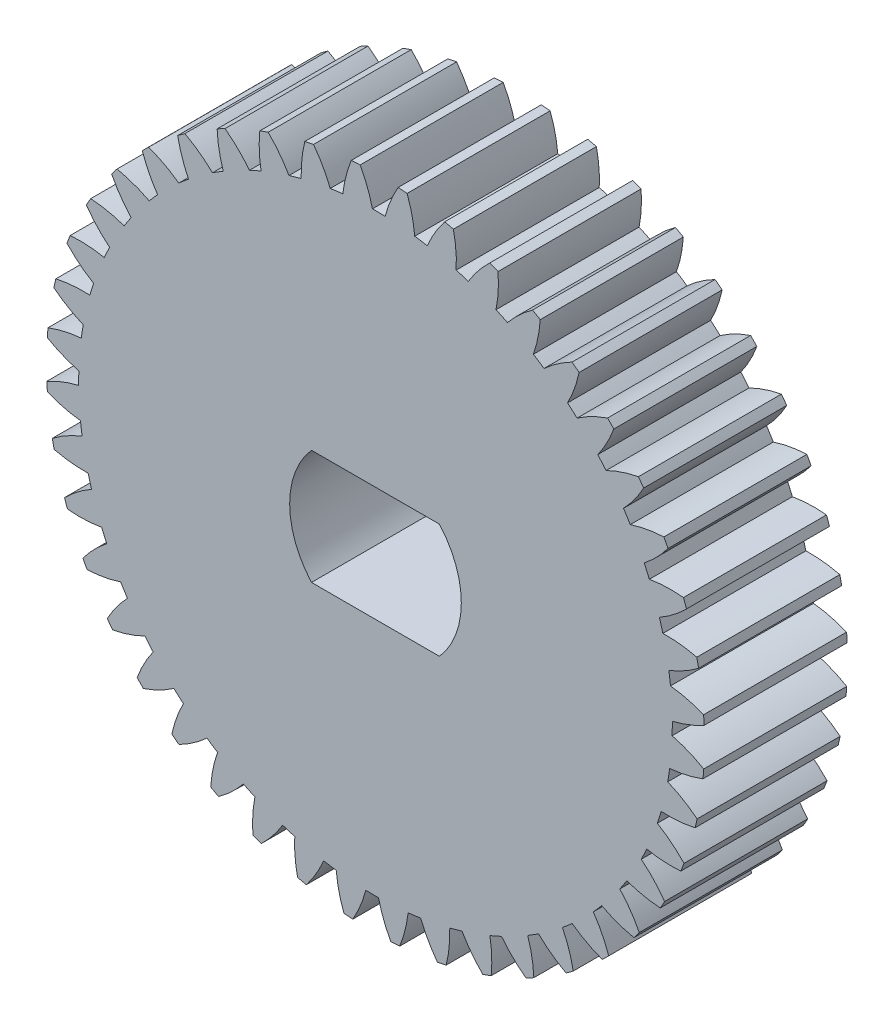
SolidWorks part; units mm, degrees
ref_plane "Front Plane" through (0, 0, 0) normal (0, 0, 1) x (1, 0, 0)
ref_plane "Top Plane" through (0, 0, 0) normal (0, 1, 0) x (1, 0, 0)
ref_plane "Right Plane" through (0, 0, 0) normal (1, 0, 0) x (0, 0, -1)
sketch "Sketch1" plane through (0, 0, 0) normal (0, 0, 1) x (1, 0, 0)
  circle A0 centre (0, 0) radius 57.1163
extrude "Boss-Extrude1" add sketch "Sketch1" along normal blind 10
extrude "Cut-Extrude5" cut sketch "Sketch6" against normal through all both and the other way through all contours A176 A703 A702 A701 A700 A699 A698 A697 A696 A695 A694 A693 A692 A691 A690 A689 A688 A687 A686 A685 A684 A683 A682 A681 A680 A679 A678 A677 A676 A675 A674 A673 A672 A671 A670 A669 A668 A667 A666 A665 A664 A663 A662 A661 A660 A659 A658 A657 A656 A655 | L0 A177 L1 A0 region at (13.1698, 8.2293, -42.7823) region at (-98.2995, 8.2293, -42.7823)
sketch "Sketch6" plane through (-165.342, -142.9681, -42.7823) normal (0, 0, 1) x (1, 0, 0)
  line L0 (174.0397, 155.1974) -> (182.984, 155.1974)
  line L1 (174.0397, 147.1974) -> (182.984, 147.1974)
  arc A0 (182.984, 147.1974) -> (182.984, 155.1974) centre (178.5118, 151.1974) ccw
  circle A176 centre (178.5118, 151.1974) radius 114.7139
  arc A177 (174.0397, 155.1974) -> (174.0397, 147.1974) centre (178.5118, 151.1974) ccw
  arc A528 (175.3501, 171.7041) -> (174.1813, 173.786) centre (167.1631, 168.4771) ccw
  arc A529 (174.1813, 173.786) -> (173.5696, 173.6601) centre (178.5118, 151.1974) ccw
  arc A530 (173.5696, 173.6601) -> (173.3181, 171.2858) centre (182.114, 171.5544) ccw
  arc A531 (173.3181, 171.2858) -> (172.4639, 171.0454) centre (178.5118, 151.1974) ccw
  arc A532 (172.4639, 171.0454) -> (171.0107, 172.9398) centre (164.8195, 166.6862) ccw
  arc A533 (171.0107, 172.9398) -> (170.4232, 172.7281) centre (178.5118, 151.1974) ccw
  arc A534 (170.4232, 172.7281) -> (170.5121, 170.3422) centre (179.1802, 171.8598) ccw
  arc A535 (170.5121, 170.3422) -> (169.7008, 169.9827) centre (178.5118, 151.1974) ccw
  arc A536 (169.7008, 169.9827) -> (167.9928, 171.651) centre (162.7545, 164.5799) ccw
  arc A537 (167.9928, 171.651) -> (167.4414, 171.3579) centre (178.5118, 151.1974) ccw
  arc A538 (167.4414, 171.3579) -> (167.8689, 169.0089) centre (176.2328, 171.7446) ccw
  arc A539 (167.8689, 169.0089) -> (167.117, 168.5375) centre (178.5118, 151.1974) ccw
  arc A540 (167.117, 168.5375) -> (165.189, 169.9458) centre (161.0104, 162.2012) ccw
  arc A541 (165.189, 169.9458) -> (164.6849, 169.5772) centre (178.5118, 151.1974) ccw
  arc A542 (164.6849, 169.5772) -> (165.4424, 167.3129) centre (173.3319, 171.2112) ccw
  arc A543 (165.4424, 167.3129) -> (164.7653, 166.7394) centre (178.5118, 151.1974) ccw
  arc A544 (164.7653, 166.7394) -> (162.6564, 167.8589) centre (159.6225, 159.5985) ccw
  arc A545 (162.6564, 167.8589) -> (162.2099, 167.4223) centre (178.5118, 151.1974) ccw
  arc A546 (162.2099, 167.4223) -> (163.2819, 165.2889) centre (170.5363, 170.2703) ccw
  arc A547 (163.2819, 165.2889) -> (162.6933, 164.6248) centre (178.5118, 151.1974) ccw
  arc A548 (162.6933, 164.6248) -> (160.4466, 165.4329) centre (158.6192, 156.8247) ccw
  arc A549 (160.4466, 165.4329) -> (160.0668, 164.9372) centre (178.5118, 151.1974) ccw
  arc A550 (160.0668, 164.9372) -> (161.4315, 162.9781) centre (167.9032, 168.9411) ccw
  arc A551 (161.4315, 162.9781) -> (160.9434, 162.2369) centre (178.5118, 151.1974) ccw
  arc A552 (160.9434, 162.2369) -> (158.6046, 162.717) centre (158.0208, 153.9364) ccw
  arc A553 (158.6046, 162.717) -> (158.2992, 162.1723) centre (178.5118, 151.1974) ccw
  arc A554 (158.2992, 162.1723) -> (159.9288, 160.4274) centre (165.486, 167.2507) ccw
  arc A555 (159.9288, 160.4274) -> (159.5511, 159.6243) centre (178.5118, 151.1974) ccw
  arc A556 (159.5511, 159.6243) -> (157.1678, 159.7667) centre (157.8396, 150.9924) ccw
  arc A557 (157.1678, 159.7667) -> (156.943, 159.184) centre (178.5118, 151.1974) ccw
  arc A558 (156.943, 159.184) -> (158.8044, 157.6888) centre (163.3339, 165.2335) ccw
  arc A559 (158.8044, 157.6888) -> (158.5448, 156.8402) centre (178.5118, 151.1974) ccw
  arc A560 (158.5448, 156.8402) -> (156.1655, 156.6419) centre (158.0792, 148.0525) ccw
  arc A561 (156.1655, 156.6419) -> (156.0259, 156.0332) centre (178.5118, 151.1974) ccw
  arc A562 (156.0259, 156.0332) -> (158.0812, 154.818) centre (161.4908, 162.9306) ccw
  arc A563 (158.0812, 154.818) -> (157.945, 153.9411) centre (178.5118, 151.1974) ccw
  arc A564 (157.945, 153.9411) -> (155.6181, 153.4063) centre (158.7347, 145.1766) ccw
  arc A565 (155.6181, 153.4063) -> (155.5666, 152.7839) centre (178.5118, 151.1974) ccw
  arc A566 (155.5666, 152.7839) -> (157.7738, 151.8736) centre (159.9943, 160.3889) ccw
  arc A567 (157.7738, 151.8736) -> (157.7639, 150.9863) centre (178.5118, 151.1974) ccw
  arc A568 (157.7639, 150.9863) -> (155.5368, 150.1257) centre (159.7929, 142.4234) ccw
  arc A569 (155.5368, 150.1257) -> (155.5744, 149.5023) centre (178.5118, 151.1974) ccw
  arc A570 (155.5744, 149.5023) -> (157.8887, 148.9154) centre (158.8747, 157.66) ccw
  arc A571 (157.8887, 148.9154) -> (158.0051, 148.0357) centre (178.5118, 151.1974) ccw
  arc A572 (158.0051, 148.0357) -> (155.9232, 146.8669) centre (161.2321, 139.8487) ccw
  arc A573 (155.9232, 146.8669) -> (156.0491, 146.2552) centre (178.5118, 151.1974) ccw
  arc A574 (156.0491, 146.2552) -> (158.4234, 146.0037) centre (158.1548, 154.7996) ccw
  arc A575 (158.4234, 146.0037) -> (158.6638, 145.1494) centre (178.5118, 151.1974) ccw
  arc A576 (158.6638, 145.1494) -> (156.7694, 143.6963) centre (163.0231, 137.505) ccw
  arc A577 (156.7694, 143.6963) -> (156.9811, 143.1087) centre (178.5118, 151.1974) ccw
  arc A578 (156.9811, 143.1087) -> (159.367, 143.1976) centre (157.8494, 151.8658) ccw
  arc A579 (159.367, 143.1976) -> (159.7266, 142.3863) centre (178.5118, 151.1974) ccw
  arc A580 (159.7266, 142.3863) -> (158.0582, 140.6784) centre (165.1293, 135.4401) ccw
  arc A581 (158.0582, 140.6784) -> (158.3514, 140.1269) centre (178.5118, 151.1974) ccw
  arc A582 (158.3514, 140.1269) -> (160.7003, 140.5545) centre (157.9646, 148.9184) ccw
  arc A583 (160.7003, 140.5545) -> (161.1717, 139.8026) centre (178.5118, 151.1974) ccw
  arc A584 (161.1717, 139.8026) -> (159.7634, 137.8746) centre (167.508, 133.696) ccw
  arc A585 (159.7634, 137.8746) -> (160.132, 137.3705) centre (178.5118, 151.1974) ccw
  arc A586 (160.132, 137.3705) -> (162.3963, 138.128) centre (158.4981, 146.0174) ccw
  arc A587 (162.3963, 138.128) -> (162.9699, 137.4508) centre (178.5118, 151.1974) ccw
  arc A588 (162.9699, 137.4508) -> (161.8503, 135.342) centre (170.1108, 132.3081) ccw
  arc A589 (161.8503, 135.342) -> (162.2869, 134.8955) centre (178.5118, 151.1974) ccw
  arc A590 (162.2869, 134.8955) -> (164.4203, 135.9675) centre (159.439, 143.2219) ccw
  arc A591 (164.4203, 135.9675) -> (165.0844, 135.3789) centre (178.5118, 151.1974) ccw
  arc A592 (165.0844, 135.3789) -> (164.2763, 133.1322) centre (172.8845, 131.3048) ccw
  arc A593 (164.2763, 133.1322) -> (164.7721, 132.7524) centre (178.5118, 151.1974) ccw
  arc A594 (164.7721, 132.7524) -> (166.7312, 134.1171) centre (160.7681, 140.5887) ccw
  arc A595 (166.7312, 134.1171) -> (167.4723, 133.629) centre (178.5118, 151.1974) ccw
  arc A596 (167.4723, 133.629) -> (166.9922, 131.2902) centre (175.7728, 130.7064) ccw
  arc A597 (166.9922, 131.2902) -> (167.5369, 130.9847) centre (178.5118, 151.1974) ccw
  arc A598 (167.5369, 130.9847) -> (169.2818, 132.6144) centre (162.4585, 138.1715) ccw
  arc A599 (169.2818, 132.6144) -> (170.0849, 132.2367) centre (178.5118, 151.1974) ccw
  arc A600 (170.0849, 132.2367) -> (169.9425, 129.8534) centre (178.7168, 130.5252) ccw
  arc A601 (169.9425, 129.8534) -> (170.5252, 129.6286) centre (178.5118, 151.1974) ccw
  arc A602 (170.5252, 129.6286) -> (172.0204, 131.49) centre (164.4757, 136.0195) ccw
  arc A603 (172.0204, 131.49) -> (172.869, 131.2304) centre (178.5118, 151.1974) ccw
  arc A604 (172.869, 131.2304) -> (173.0673, 128.8511) centre (181.6567, 130.7648) ccw
  arc A605 (173.0673, 128.8511) -> (173.676, 128.7115) centre (178.5118, 151.1974) ccw
  arc A606 (173.676, 128.7115) -> (174.8912, 130.7667) centre (166.7786, 134.1764) ccw
  arc A607 (174.8912, 130.7667) -> (175.7681, 130.6306) centre (178.5118, 151.1974) ccw
  arc A608 (175.7681, 130.6306) -> (176.3029, 128.3037) centre (184.5326, 131.4203) ccw
  arc A609 (176.3029, 128.3037) -> (176.9253, 128.2522) centre (178.5118, 151.1974) ccw
  arc A610 (176.9253, 128.2522) -> (177.8356, 130.4594) centre (169.3203, 132.6798) ccw
  arc A611 (177.8356, 130.4594) -> (178.723, 130.4495) centre (178.5118, 151.1974) ccw
  arc A612 (178.723, 130.4495) -> (179.5835, 128.2224) centre (187.2859, 132.4784) ccw
  arc A613 (179.5835, 128.2224) -> (180.2069, 128.2599) centre (178.5118, 151.1974) ccw
  arc A614 (180.2069, 128.2599) -> (180.7938, 130.5743) centre (172.0492, 131.5602) ccw
  arc A615 (180.7938, 130.5743) -> (181.6735, 130.6907) centre (178.5118, 151.1974) ccw
  arc A616 (181.6735, 130.6907) -> (182.8423, 128.6087) centre (189.8605, 133.9176) ccw
  arc A617 (182.8423, 128.6087) -> (183.454, 128.7346) centre (178.5118, 151.1974) ccw
  arc A618 (183.454, 128.7346) -> (183.7056, 131.1089) centre (174.9097, 130.8404) ccw
  arc A619 (183.7056, 131.1089) -> (184.5598, 131.3494) centre (178.5118, 151.1974) ccw
  arc A620 (184.5598, 131.3494) -> (186.0129, 129.455) centre (192.2042, 135.7086) ccw
  arc A621 (186.0129, 129.455) -> (186.6005, 129.6666) centre (178.5118, 151.1974) ccw
  arc A622 (186.6005, 129.6666) -> (186.5116, 132.0525) centre (177.8434, 130.535) ccw
  arc A623 (186.5116, 132.0525) -> (187.3229, 132.4121) centre (178.5118, 151.1974) ccw
  arc A624 (187.3229, 132.4121) -> (189.0308, 130.7438) centre (194.2691, 137.8149) ccw
  arc A625 (189.0308, 130.7438) -> (189.5823, 131.0369) centre (178.5118, 151.1974) ccw
  arc A626 (189.5823, 131.0369) -> (189.1547, 133.3859) centre (180.7908, 130.6501) ccw
  arc A627 (189.1547, 133.3859) -> (189.9066, 133.8573) centre (178.5118, 151.1974) ccw
  arc A628 (189.9066, 133.8573) -> (191.8346, 132.449) centre (196.0132, 140.1936) ccw
  arc A629 (191.8346, 132.449) -> (192.3387, 132.8176) centre (178.5118, 151.1974) ccw
  arc A630 (192.3387, 132.8176) -> (191.5813, 135.0818) centre (183.6918, 131.1836) ccw
  arc A631 (191.5813, 135.0818) -> (192.2584, 135.6554) centre (178.5118, 151.1974) ccw
  arc A632 (192.2584, 135.6554) -> (194.3672, 134.5358) centre (197.4011, 142.7963) ccw
  arc A633 (194.3672, 134.5358) -> (194.8137, 134.9725) centre (178.5118, 151.1974) ccw
  arc A634 (194.8137, 134.9725) -> (193.7417, 137.1058) centre (186.4873, 132.1245) ccw
  arc A635 (193.7417, 137.1058) -> (194.3303, 137.77) centre (178.5118, 151.1974) ccw
  arc A636 (194.3303, 137.77) -> (196.577, 136.9619) centre (198.4044, 145.5701) ccw
  arc A637 (196.577, 136.9619) -> (196.9568, 137.4576) centre (178.5118, 151.1974) ccw
  arc A638 (196.9568, 137.4576) -> (195.5921, 139.4167) centre (189.1205, 133.4537) ccw
  arc A639 (195.5921, 139.4167) -> (196.0802, 140.1578) centre (178.5118, 151.1974) ccw
  arc A640 (196.0802, 140.1578) -> (198.419, 139.6777) centre (199.0028, 148.4584) ccw
  arc A641 (198.419, 139.6777) -> (198.7245, 140.2225) centre (178.5118, 151.1974) ccw
  arc A642 (198.7245, 140.2225) -> (197.0948, 141.9674) centre (191.5377, 135.1441) ccw
  arc A643 (197.0948, 141.9674) -> (197.4725, 142.7704) centre (178.5118, 151.1974) ccw
  arc A644 (197.4725, 142.7704) -> (199.8558, 142.6281) centre (199.184, 151.4024) ccw
  arc A645 (199.8558, 142.6281) -> (200.0806, 143.2107) centre (178.5118, 151.1974) ccw
  arc A646 (200.0806, 143.2107) -> (198.2193, 144.706) centre (193.6897, 137.1612) ccw
  arc A647 (198.2193, 144.706) -> (198.4788, 145.5546) centre (178.5118, 151.1974) ccw
  arc A648 (198.4788, 145.5546) -> (200.8581, 145.7529) centre (198.9445, 154.3423) ccw
  arc A649 (200.8581, 145.7529) -> (200.9977, 146.3616) centre (178.5118, 151.1974) ccw
  arc A650 (200.9977, 146.3616) -> (198.9425, 147.5767) centre (195.5328, 139.4641) ccw
  arc A651 (198.9425, 147.5767) -> (199.0786, 148.4536) centre (178.5118, 151.1974) ccw
  arc A652 (199.0786, 148.4536) -> (201.4055, 148.9885) centre (198.2889, 157.2181) ccw
  arc A653 (201.4055, 148.9885) -> (201.457, 149.6109) centre (178.5118, 151.1974) ccw
  arc A654 (201.457, 149.6109) -> (199.2498, 150.5212) centre (197.0294, 142.0059) ccw
  arc A655 (199.2498, 150.5212) -> (199.2597, 151.4085) centre (178.5118, 151.1974) ccw
  arc A656 (199.2597, 151.4085) -> (201.4868, 152.2691) centre (197.2308, 159.9714) ccw
  arc A657 (201.4868, 152.2691) -> (201.4493, 152.8925) centre (178.5118, 151.1974) ccw
  arc A658 (201.4493, 152.8925) -> (199.135, 153.4794) centre (198.149, 144.7348) ccw
  arc A659 (199.135, 153.4794) -> (199.0185, 154.3591) centre (178.5118, 151.1974) ccw
  arc A660 (199.0185, 154.3591) -> (201.1005, 155.5279) centre (195.7916, 162.5461) ccw
  arc A661 (201.1005, 155.5279) -> (200.9746, 156.1396) centre (178.5118, 151.1974) ccw
  arc A662 (200.9746, 156.1396) -> (198.6003, 156.3911) centre (198.8688, 147.5952) ccw
  arc A663 (198.6003, 156.3911) -> (198.3598, 157.2453) centre (178.5118, 151.1974) ccw
  arc A664 (198.3598, 157.2453) -> (200.2543, 158.6985) centre (194.0006, 164.8898) ccw
  arc A665 (200.2543, 158.6985) -> (200.0426, 159.286) centre (178.5118, 151.1974) ccw
  arc A666 (200.0426, 159.286) -> (197.6567, 159.1971) centre (199.1743, 150.529) ccw
  arc A667 (197.6567, 159.1971) -> (197.2971, 160.0084) centre (178.5118, 151.1974) ccw
  arc A668 (197.2971, 160.0084) -> (198.9654, 161.7164) centre (191.8943, 166.9547) ccw
  arc A669 (198.9654, 161.7164) -> (198.6723, 162.2679) centre (178.5118, 151.1974) ccw
  arc A670 (198.6723, 162.2679) -> (196.3233, 161.8403) centre (199.0591, 153.4764) ccw
  arc A671 (196.3233, 161.8403) -> (195.8519, 162.5922) centre (178.5118, 151.1974) ccw
  arc A672 (195.8519, 162.5922) -> (197.2602, 164.5202) centre (189.5156, 168.6988) ccw
  arc A673 (197.2602, 164.5202) -> (196.8916, 165.0243) centre (178.5118, 151.1974) ccw
  arc A674 (196.8916, 165.0243) -> (194.6274, 164.2668) centre (198.5256, 156.3773) ccw
  arc A675 (194.6274, 164.2668) -> (194.0538, 164.944) centre (178.5118, 151.1974) ccw
  arc A676 (194.0538, 164.944) -> (195.1734, 167.0528) centre (186.9129, 170.0867) ccw
  arc A677 (195.1734, 167.0528) -> (194.7367, 167.4993) centre (178.5118, 151.1974) ccw
  arc A678 (194.7367, 167.4993) -> (192.6034, 166.4273) centre (197.5847, 159.1729) ccw
  arc A679 (192.6034, 166.4273) -> (191.9393, 167.0159) centre (178.5118, 151.1974) ccw
  arc A680 (191.9393, 167.0159) -> (192.7473, 169.2626) centre (184.1392, 171.09) ccw
  arc A681 (192.7473, 169.2626) -> (192.2516, 169.6424) centre (178.5118, 151.1974) ccw
  arc A682 (192.2516, 169.6424) -> (190.2925, 168.2777) centre (196.2555, 161.806) ccw
  arc A683 (190.2925, 168.2777) -> (189.5514, 168.7658) centre (178.5118, 151.1974) ccw
  arc A684 (189.5514, 168.7658) -> (190.0315, 171.1046) centre (181.2509, 171.6884) ccw
  arc A685 (190.0315, 171.1046) -> (189.4867, 171.41) centre (178.5118, 151.1974) ccw
  arc A686 (189.4867, 171.41) -> (187.7418, 169.7804) centre (194.5652, 164.2233) ccw
  arc A687 (187.7418, 169.7804) -> (186.9388, 170.1581) centre (178.5118, 151.1974) ccw
  arc A688 (186.9388, 170.1581) -> (187.0811, 172.5414) centre (178.3068, 171.8696) ccw
  arc A689 (187.0811, 172.5414) -> (186.4985, 172.7662) centre (178.5118, 151.1974) ccw
  arc A690 (186.4985, 172.7662) -> (185.0032, 170.9048) centre (192.548, 166.3753) ccw
  arc A691 (185.0032, 170.9048) -> (184.1546, 171.1644) centre (178.5118, 151.1974) ccw
  arc A692 (184.1546, 171.1644) -> (183.9563, 173.5437) centre (175.3669, 171.63) ccw
  arc A693 (183.9563, 173.5437) -> (183.3476, 173.6833) centre (178.5118, 151.1974) ccw
  arc A694 (183.3476, 173.6833) -> (182.1325, 171.628) centre (190.2451, 168.2184) ccw
  arc A695 (182.1325, 171.628) -> (181.2556, 171.7642) centre (178.5118, 151.1974) ccw
  arc A696 (181.2556, 171.7642) -> (180.7207, 174.0911) centre (172.4911, 170.9745) ccw
  arc A697 (180.7207, 174.0911) -> (180.0983, 174.1426) centre (178.5118, 151.1974) ccw
  arc A698 (180.0983, 174.1426) -> (179.188, 171.9354) centre (187.7033, 169.7149) ccw
  arc A699 (179.188, 171.9354) -> (178.3007, 171.9453) centre (178.5118, 151.1974) ccw
  arc A700 (178.3007, 171.9453) -> (177.4401, 174.1724) centre (169.7378, 169.9163) ccw
  arc A701 (177.4401, 174.1724) -> (176.8167, 174.1348) centre (178.5118, 151.1974) ccw
  arc A702 (176.8167, 174.1348) -> (176.2298, 171.8205) centre (184.9744, 170.8345) ccw
  arc A703 (176.2298, 171.8205) -> (175.3501, 171.7041) centre (178.5118, 151.1974) ccw
